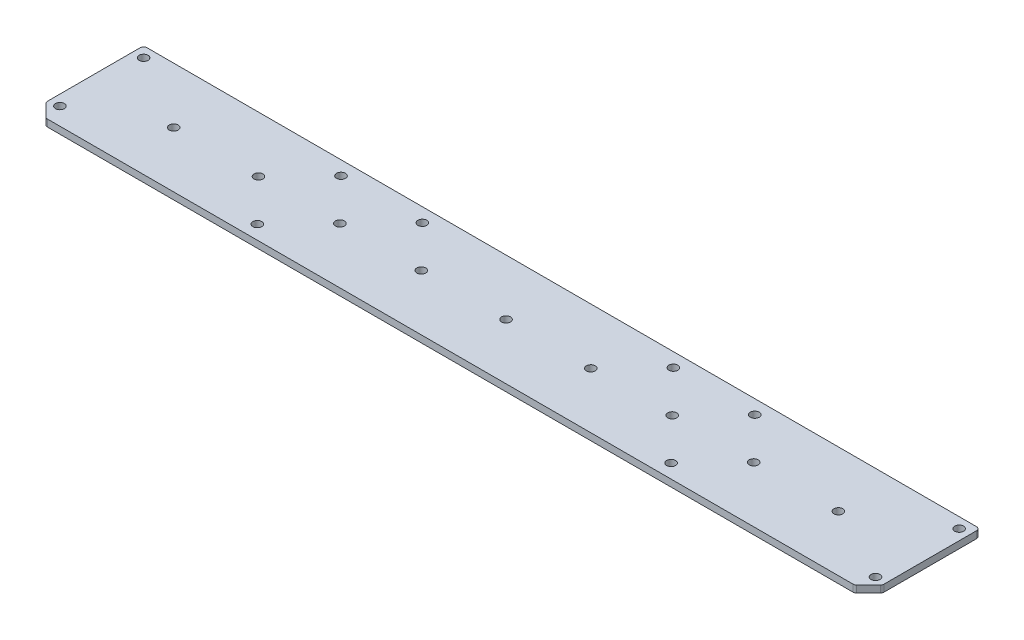
SolidWorks part; units mm, degrees
ref_plane "Front Plane" through (0, 0, 0) normal (0, 0, 1) x (1, 0, 0)
ref_plane "Top Plane" through (0, 0, 0) normal (0, 1, 0) x (1, 0, 0)
ref_plane "Right Plane" through (0, 0, 0) normal (1, 0, 0) x (0, 0, -1)
sketch "Sketch2" plane through (0, 0, 0) normal (0, 1, 0) x (1, 0, 0)
  line L0 (0, 7.0076) -> (0, 50.8)
  line L1 (0, 50.8) -> (381, 50.8)
  line L2 (381, 50.8) -> (381, 7.0076)
  line L3 (373.9924, 0) -> (7.0076, 0)
  line L4 (5.885, 0.465) -> (0.465, 5.885) construction
  line L5 (5.885, 0.465) -> (0.465, 5.885)
  line L6 (375.115, 0.465) -> (380.535, 5.885) construction
  line L7 (375.115, 0.465) -> (380.535, 5.885)
  line L8 (336.537, 50.8) -> (379.4125, 50.8) construction
  line L9 (0, 7.0076) -> (0, 50.6654) construction
  arc A2 (5.885, 0.465) -> (7.0076, 0) centre (7.0076, 1.5875) ccw
  arc A3 (0, 7.0076) -> (0.465, 5.885) centre (1.5875, 7.0076) ccw
  arc A4 (373.9924, 0) -> (375.115, 0.465) centre (373.9924, 1.5875) ccw construction
  arc A6 (373.9924, 0) -> (375.115, 0.465) centre (373.9924, 1.5875) ccw
  arc A8 (380.535, 5.885) -> (381, 7.0076) centre (379.4125, 7.0076) ccw construction
  arc A9 (380.535, 5.885) -> (381, 7.0076) centre (379.4125, 7.0076) ccw
  arc A10 (0, 7.0076) -> (0.465, 5.885) centre (1.5875, 7.0076) ccw construction
  arc A11 (5.885, 0.465) -> (7.0076, 0) centre (7.0076, 1.5875) ccw construction
extrude "Boss-Extrude1" add sketch "Sketch2" along normal blind 3.175
sketch "Sketch3" plane through (0, 0, 0) normal (0, 1, 0) x (1, 0, 0)
  circle A25 centre (4.7625, 7.9375) radius 2.032 construction
  circle A31 centre (4.7625, 46.0375) radius 2.032 construction
  circle A63 centre (376.2375, 7.9375) radius 2.032 construction
  circle A64 centre (376.2375, 46.0375) radius 2.032 construction
  circle A67 centre (4.7625, 7.9375) radius 2.032
  circle A68 centre (4.7625, 46.0375) radius 2.032
  circle A72 centre (376.2375, 7.9375) radius 2.032
  circle A73 centre (376.2375, 46.0375) radius 2.032
  circle A123 centre (341.884, 25.4) radius 2.032 construction
  circle A124 centre (247.65, 44.45) radius 2.032 construction
  circle A125 centre (284.734, 44.45) radius 2.032 construction
  circle A129 centre (284.734, 6.35) radius 2.032 construction
  circle A132 centre (190.5, 25.4) radius 2.032 construction
  circle A135 centre (133.35, 44.45) radius 2.032 construction
  circle A136 centre (96.266, 44.45) radius 2.032 construction
  circle A137 centre (96.266, 6.35) radius 2.032 construction
  circle A140 centre (77.724, 25.4) radius 2.032 construction
  circle A141 centre (39.116, 25.4) radius 2.032 construction
  circle A142 centre (341.884, 25.4) radius 2.032
  circle A143 centre (247.65, 44.45) radius 2.032
  circle A144 centre (284.734, 44.45) radius 2.032
  circle A148 centre (284.734, 6.35) radius 2.032
  circle A151 centre (190.5, 25.4) radius 2.032
  circle A154 centre (133.35, 44.45) radius 2.032
  circle A155 centre (96.266, 44.45) radius 2.032
  circle A156 centre (96.266, 6.35) radius 2.032
  circle A159 centre (77.724, 25.4) radius 2.032
  circle A160 centre (39.116, 25.4) radius 2.032
  circle A161 centre (151.892, 25.4) radius 2.032
  circle A162 centre (229.108, 25.4) radius 2.032
  circle A163 centre (266.192, 25.4) radius 2.032
  circle A164 centre (303.276, 25.4) radius 2.032
  circle A165 centre (151.892, 25.4) radius 2.3813 construction
  circle A166 centre (229.108, 25.4) radius 2.3813 construction
  circle A167 centre (266.192, 25.4) radius 2.3813 construction
  circle A168 centre (303.276, 25.4) radius 2.3813 construction
  circle A170 centre (114.808, 25.4) radius 2.032 construction
  circle A171 centre (114.808, 25.4) radius 2.032
extrude "Cut-Extrude1" cut sketch "Sketch3" along normal through all
fillet "Fillet1" radius 1.5875 2 edges at (0, 1.5875, -50.8) (381, 1.5875, -50.8)
